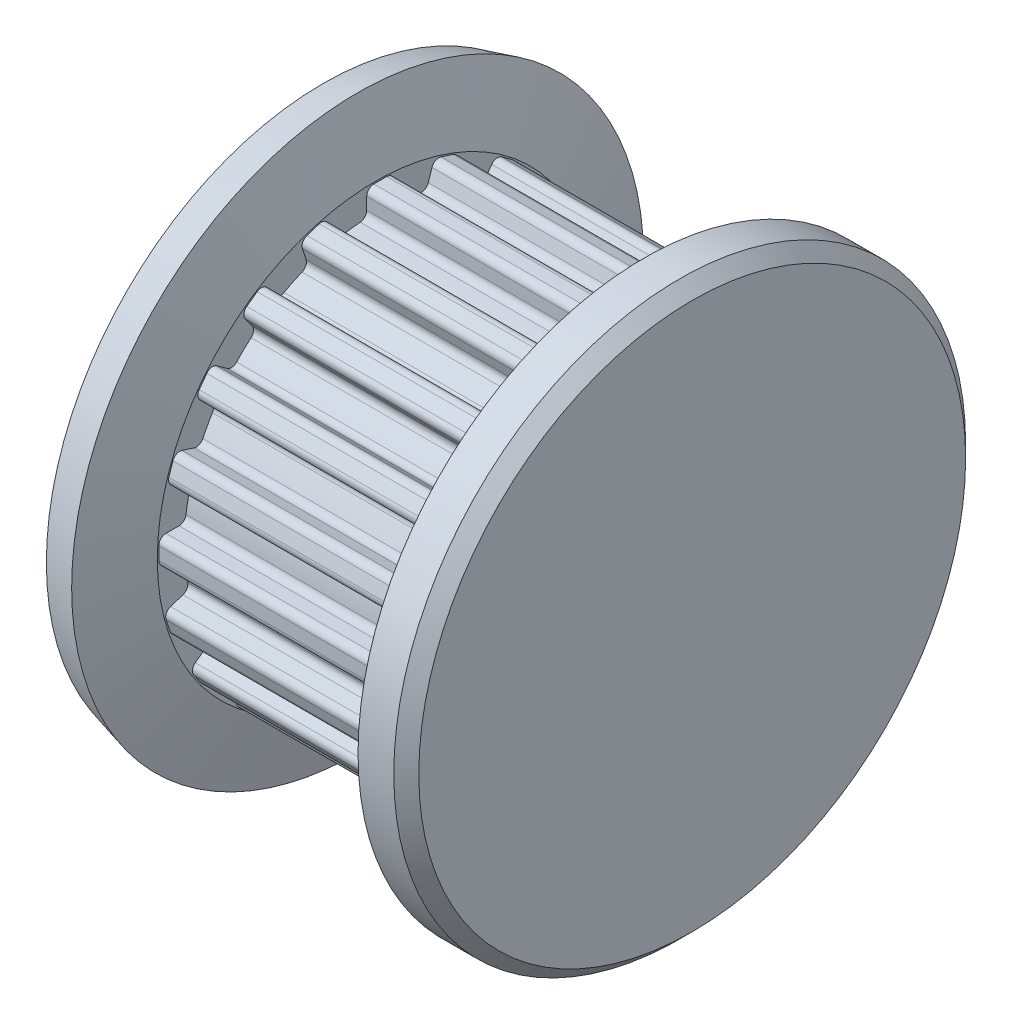
SolidWorks part; units mm, degrees
material "2024-T4"
ref_plane "Front Plane" through (0, 0, 0) normal (0, 0, 1) x (1, 0, 0)
ref_plane "Top Plane" through (0, 0, 0) normal (0, 1, 0) x (1, 0, 0)
ref_plane "Right Plane" through (0, 0, 0) normal (1, 0, 0) x (0, 0, -1)
sketch "Sketch1" plane through (0, 0, 0) normal (0, 0, 1) x (1, 0, 0)
  line L0 (-7.0776, 0) -> (2.0788, 0)
  line L1 (2.4288, 0.35) -> (2.4288, 5.15)
  line L2 (2.0788, 5.5) -> (1.0788, 5.5)
  line L3 (0.5724, 3.61) -> (0.5724, 2.85)
  line L4 (0.5724, 2.85) -> (-6.4276, 2.85)
  line L5 (-7.4276, 2.85) -> (-7.4276, 0.35)
  line L6 (-7.4276, -2.5) -> (8.5724, -2.5) construction
  line L7 (-8.4276, 2.85) -> (-8.4276, -12.6573) construction
  line L8 (-8.4276, 2.85) -> (-8.4276, 0) construction
  line L9 (0.5724, 5.5) -> (-12.4584, 5.5) construction
  line L10 (0.5724, 3.61) -> (-7.4276, 3.61) construction
  line L11 (-6.4276, 2.85) -> (-6.4276, 3.61)
  line L12 (-6.4276, 3.61) -> (-6.9341, 5.5)
  line L13 (-7.4276, 2.85) -> (-7.4276, 3.4783)
  line L14 (-7.4276, 3.4783) -> (-7.9, 5.2412)
  line L15 (-7.9, 5.2412) -> (-6.9341, 5.5)
  line L16 (-7.4276, 0) -> (8.5724, 0) construction
  line L17 (2.0788, 0) -> (2.4288, 0.35)
  line L18 (-7.4276, 2.85) -> (-7.4276, 0) construction
  line L19 (-7.4276, 0.35) -> (-7.0776, 0)
  line L20 (2.4288, 5.15) -> (2.0788, 5.5)
  line L21 (0.5724, 2.85) -> (-7.4276, 2.85) construction
  line L22 (1.0788, 5.5) -> (0.5724, 3.61)
  point P4 (2.4288, 5.5)
  dimension "D2" = 8
  dimension "D3" = 2.5
  dimension "D4" = 8
  dimension "D5" = 5.35
  dimension "D8" = 1
  dimension "D9" = 195
  dimension "D11" = 1.89
  dimension "D12" = 15
  dimension "D13" = 1
  dimension "D14" = 0.495
  dimension "D15" = 0.495
  dimension "D16" = 135
  dimension "D18" = 135
  dimension "D6" = 1
  dimension "D7" = 0.76
  dimension "D10" = 1
revolve "Revolve2" add sketch "Sketch1" angle 360 about L6 region at (-2.3293, 1.9622, 0)
sketch "Sketch2" plane through (0.5724, 0, 0) normal (-1, 0, 0) x (0, 0, 1)
  line L1 (-0.51, 2.8066) -> (0.25, 2.8066)
  line L2 (-0.51, 2.8066) -> (-0.51, 3.5666)
  line L3 (-0.51, 3.5666) -> (0.25, 3.5666)
  line L4 (0.25, 2.8066) -> (0.25, 3.5666)
  dimension "D1" = 0.76
  dimension "D2" = 0.76
extrude "Boss-Extrude1" add sketch "Sketch2" along normal up to surface (7 mm away) up to face at (-6.4276, -2.5, 6.11)
fillet "Fillet1" radius 0.2 4 edges at (-2.9276, 2.8256, -0.51) (-2.9276, 2.8442, 0.25) (-2.9276, 3.5666, -0.51) (-2.9276, 3.5666, 0.25)
pattern_circular "CirPattern2" count 20 over 360 about axis through (-7.4276, -2.5, 0) along (-1, 0, 0) of "Boss-Extrude1", "Fillet1"
sketch "Sketch3" plane through (0, 0, 0) normal (0, 1, 0) x (1, 0, 0)
  line L0 (1.0788, -8) -> (2.0788, -8) construction
  line L3 (1.5788, -8) -> (1.5788, 8) construction
  line L4 (2.0788, 8) -> (1.0788, 8) construction
  circle A0 centre (1.5788, 0) radius 1.5
extrude "Cut-Extrude2" [suppressed] cut sketch "Sketch3" against normal blind 3 and the other way blind 9 contours A0
pattern_circular "CirPattern3" [suppressed] count 2 every 90 of bodies 106
sketch "Sketch4" plane through (2.4288, 0, 0) normal (1, 0, 0) x (0, 0, -1)
  circle A0 centre (0, -2.5) radius 2.85
  circle A1 centre (0, -2.5) radius 2.85 construction
extrude "Boss-Extrude2" add sketch "Sketch4" against normal up to surface (9.8564 mm away) up to face at (-7.4276, -2.5, 5.9783)
